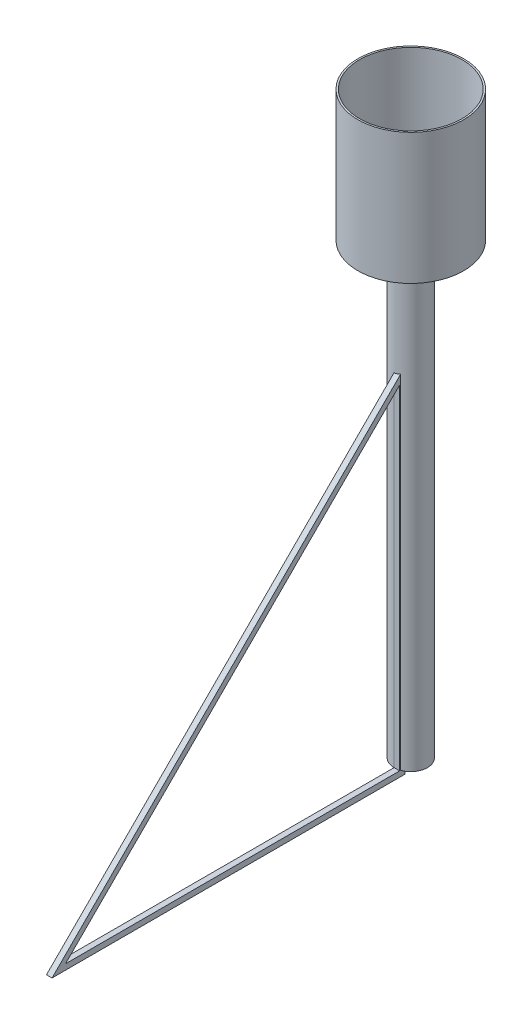
SolidWorks part; units mm, degrees
ref_plane "Front Plane" through (0, 0, 0) normal (0, 0, 1) x (1, 0, 0)
ref_plane "Top Plane" through (0, 0, 0) normal (0, 1, 0) x (1, 0, 0)
ref_plane "Right Plane" through (0, 0, 0) normal (1, 0, 0) x (0, 0, -1)
sketch "Sketch1" plane through (0, 0, 0) normal (0, 1, 0) x (1, 0, 0)
  circle A0 centre (0, 0) radius 95
  point P3 (0, 0)
  dimension "D1" = 190
extrude "Boss-Extrude1" add sketch "Sketch1" along normal blind 235
sketch "Sketch2" plane through (0, 0, 0) normal (0, -1, 0) x (1, 0, 0)
  circle A0 centre (0, 0) radius 30
  dimension "D1" = 60
extrude "Boss-Extrude2" add sketch "Sketch2" along normal blind 805
sketch "Sketch6" plane through (0, 235, 0) normal (0, 1, 0) x (1, 0, 0)
shell "Shell1" thickness 3 removed face at (0, 235, 95) removed face at (0, -805, -30)
ref_plane "Plane1" through (0, 0, 30) normal (0, 0, 1) x (1, 0, 0)
sketch "Sketch8" plane through (0, 0, 30) normal (0, 0, 1) x (1, 0, 0)
  line L0 (-30, -805) -> (30, -805) construction
  line L1 (0, -805) -> (10, -805)
  line L2 (0, -805) -> (0, -205)
  line L3 (0, -205) -> (10, -205)
  line L4 (10, -805) -> (10, -205)
  dimension "D1" = 600
  dimension "D2" = 10
ref_plane "Plane2" through (30, 0, 0) normal (1, 0, 0) x (0, 0, -1)
sketch "Sketch9" plane through (30, 0, 0) normal (1, 0, 0) x (0, 0, -1)
  line L0 (-30, -805) -> (30, -805) construction
  line L1 (0, -805) -> (10, -805)
  line L2 (0, -805) -> (0, -205)
  line L3 (0, -205) -> (10, -205)
  line L4 (10, -805) -> (10, -205)
  dimension "D1" = 600
  dimension "D2" = 10
sketch "Sketch10" plane through (0, 0, 0) normal (1, 0, 0) x (0, 0, -1)
  line L0 (-30, -205) -> (-630, -805)
  line L1 (-30, -805) -> (-30, -205) construction
  line L2 (-30, -805) -> (-30, -205) construction
  line L3 (-630, -805) -> (-30, -805)
  line L4 (-30, -205) -> (-30, -805)
  dimension "D1" = 600
extrude "Extrude-Thin1" add sketch "Sketch10" along normal blind 10 separate body thin thin type one direction wall 10
